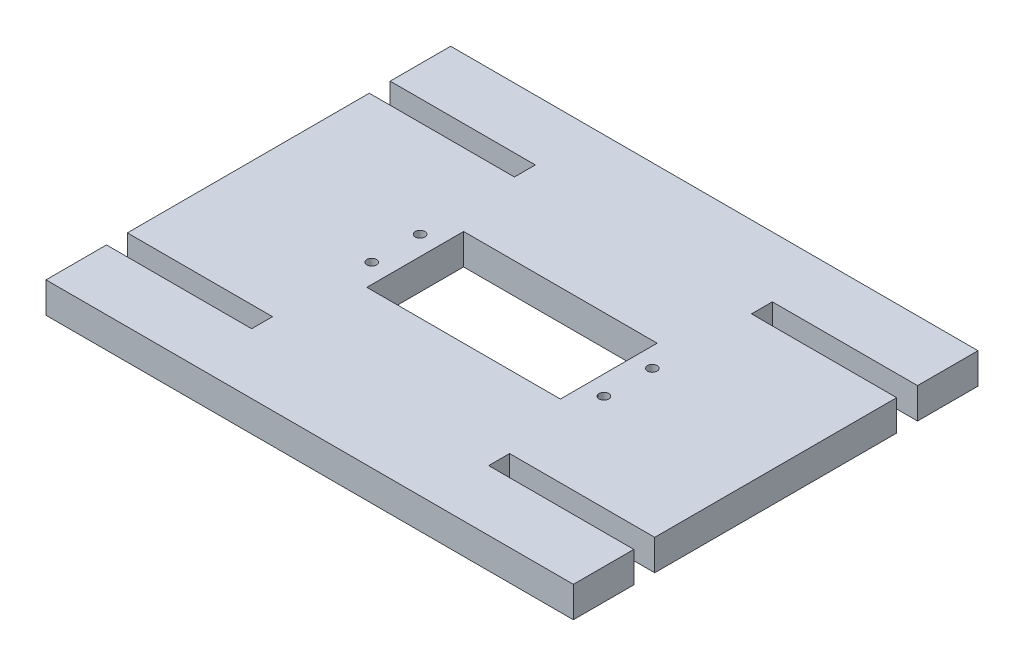
SolidWorks part; units mm, degrees
material "Balsa"
ref_plane "Front Plane" through (0, 0, 0) normal (0, 0, 1) x (1, 0, 0)
ref_plane "Top Plane" through (0, 0, 0) normal (0, 1, 0) x (1, 0, 0)
ref_plane "Right Plane" through (0, 0, 0) normal (1, 0, 0) x (0, 0, -1)
sketch "Sketch1" plane through (0, 0, 0) normal (0, 1, 0) x (1, 0, 0)
  line L0 (0, 66.818) -> (0, 16.818)
  line L1 (0, 83.636) -> (109, 83.636)
  line L2 (0, 83.636) -> (0, 71.136)
  line L3 (0, 0) -> (109, 0)
  line L4 (109, 83.636) -> (109, 71.136)
  line L5 (0, 71.136) -> (30, 71.136)
  line L6 (0, 12.5) -> (0, 0)
  line L7 (0, 66.818) -> (30, 66.818)
  line L8 (30, 71.136) -> (30, 66.818)
  line L9 (109, 66.818) -> (79, 66.818)
  line L11 (109, 71.136) -> (79, 71.136)
  line L12 (79, 66.818) -> (79, 71.136)
  line L13 (0, 16.818) -> (30, 16.818)
  line L14 (109, 12.5) -> (109, 0)
  line L15 (0, 12.5) -> (30, 12.5)
  line L16 (30, 16.818) -> (30, 12.5)
  line L17 (109, 12.5) -> (79, 12.5)
  line L18 (109, 66.818) -> (109, 16.818)
  line L19 (109, 16.818) -> (79, 16.818)
  line L20 (79, 12.5) -> (79, 16.818)
  dimension "D1" = 12.5
  dimension "D2" = 109
  dimension "D3" = 4.318
  dimension "D4" = 30
  dimension "D5" = 50
extrude "main shape" add sketch "Sketch1" along normal blind 6.35
sketch "Sketch2" plane through (0, 6.35, 0) normal (0, 1, 0) x (1, 0, 0)
  line L0 (0, 66.818) -> (109, 16.818) construction
  line L1 (34.5, 51.818) -> (74.5, 51.818)
  line L2 (34.5, 51.818) -> (34.5, 31.818)
  line L3 (34.5, 31.818) -> (74.5, 31.818)
  line L4 (74.5, 51.818) -> (74.5, 31.818)
  line L5 (109, 66.818) -> (0, 16.818) construction
  line L6 (0, 66.818) -> (0, 16.818) construction
  line L7 (0, 16.818) -> (30, 16.818) construction
  line L8 (34.5, 51.818) -> (74.5, 31.818) construction
  line L9 (74.5, 51.818) -> (34.5, 31.818) construction
  line L10 (30.5, 41.818) -> (78.5, 41.818) construction
  line L11 (34.5, 51.818) -> (30.5, 51.818) construction
  line L12 (34.5, 51.818) -> (34.5, 31.818) construction
  line L13 (34.5, 31.818) -> (30.5, 31.818) construction
  line L14 (30.5, 51.818) -> (30.5, 31.818) construction
  line L15 (74.5, 51.818) -> (78.5, 51.818) construction
  line L16 (74.5, 51.818) -> (74.5, 31.818) construction
  line L17 (74.5, 31.818) -> (78.5, 31.818) construction
  line L18 (78.5, 51.818) -> (78.5, 31.818) construction
  point P15 (54.5, 41.818)
  point P16 (54.5, 41.818)
  point P27 (30.5, 36.818)
  point P28 (30.5, 46.818)
  point P29 (78.5, 36.818)
  point P30 (78.5, 46.818)
  dimension "D1" = 40
  dimension "D2" = 20
  dimension "D3" = 48
  dimension "D4" = 20
  dimension "D5" = 10
  dimension "D6" = 5
  dimension "D7" = 10
  dimension "D8" = 5
extrude "cut for servo + mounting hole locations" cut sketch "Sketch2" against normal through all
hole_wizard "#3-48 Tapped Hole1" positions "Sketch4" profile "Sketch3" tap size "#3-48" standard "Ansi Inch"
sketch "Sketch4" plane through (0, 6.35, 0) normal (0, 1, 0) x (-1, 0, 0)
  point P16 (-30.5, -36.818)
  point P19 (-30.5, -46.818)
  point P22 (-78.5, -36.818)
  point P25 (-78.5, -46.818)
cosmetic thread "Hole Thread5" parameters "D1"=5.03, "D2"=2.5146
cosmetic thread "Hole Thread6" parameters "D1"=5.03, "D2"=2.5146
cosmetic thread "Hole Thread7" parameters "D1"=5.03, "D2"=2.5146
cosmetic thread "Hole Thread8" parameters "D1"=5.03, "D2"=2.5146
sketch "Sketch3" plane through (30.5, 6.35, -36.818) normal (1, 0, 0) x (0, 0, 1)
  line L0 (0, 0) -> (0, 8.269)
  line L1 (0, 8.269) -> (0.9969, 7.67)
  line L2 (0.9969, 7.67) -> (0.9969, 0)
  line L5 (0.9969, 0) -> (0, 0)
  line L10 (0, 8.269) -> (-0.997, 7.67) construction
  line L11 (0, -6.35) -> (0, 107.95) construction
  dimension "Tap Drill Dia." = 1.9939
  dimension "Tap Drill Depth" = 7.67
  dimension "Drill Angle" = 118
ref_axis "Axis1" through (54.5, 6.35, -41.818) along (0, 1, 0)
